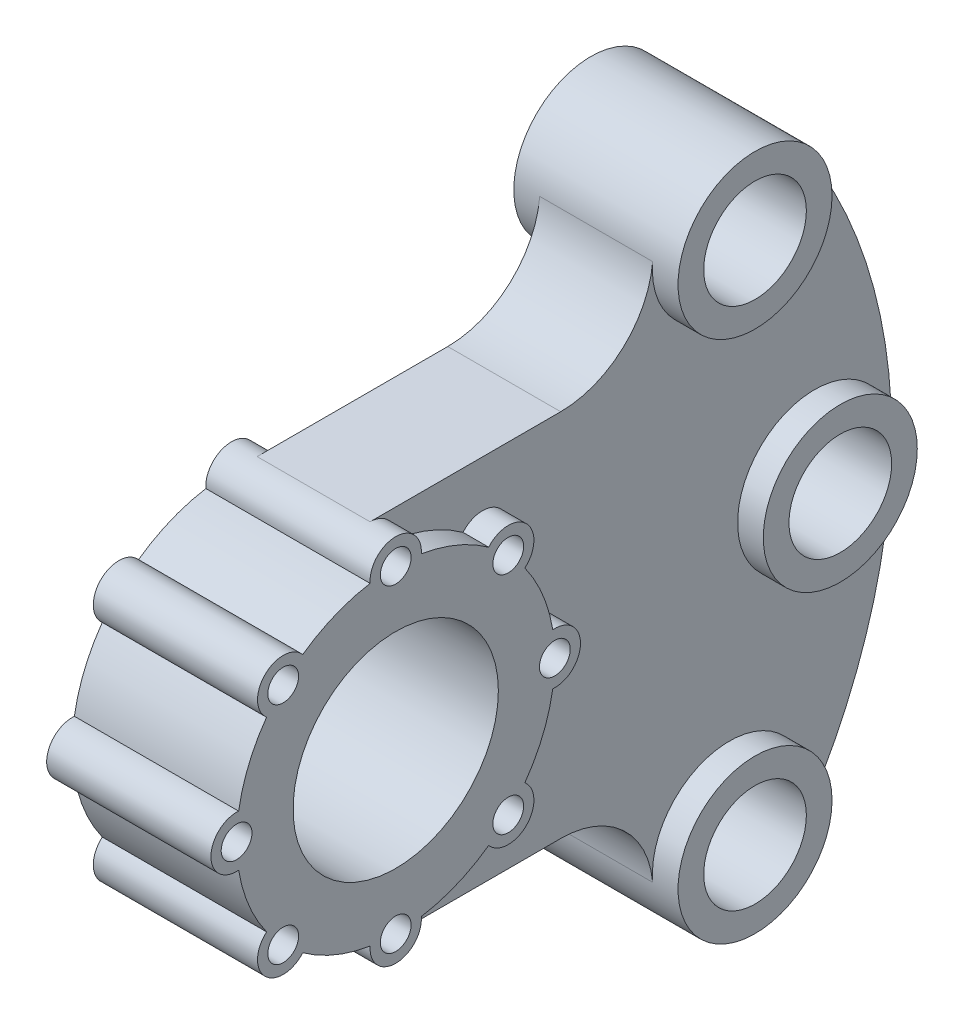
SolidWorks part; units mm, degrees
ref_plane "Front Plane" through (0, 0, 0) normal (1, 0, 0) x (0, 1, 0)
ref_plane "Top Plane" through (0, 0, 0) normal (0, 0, 1) x (0, 1, 0)
ref_plane "Right Plane" through (0, 0, 0) normal (0, 1, 0) x (-1, 0, 0)
sketch "Sketch1" plane through (0, 0, 0) normal (1, 0, 0) x (0, 1, 0)
  line L0 (0, 0) -> (0, -108.5292) construction
  line L2 (51, -70) -> (36, -70) construction
  line L3 (36, 0) -> (36, -5) construction
  line L4 (-36, 0) -> (-36, -37.1366)
  line L5 (36, 0) -> (36, -37.1366)
  circle A0 centre (0, 0) radius 20
  arc A1 (-4.9837, 30.5968) -> (-18.1112, 25.1592) centre (0, 0) ccw
  arc A2 (4.9837, 30.5968) -> (-4.9837, 30.5968) centre (0, 31) ccw
  circle A3 centre (0, 31) radius 3
  arc A4 (25.1592, 18.1112) -> (18.1112, 25.1592) centre (21.9203, 21.9203) ccw
  circle A5 centre (21.9203, 21.9203) radius 3
  arc A6 (30.5968, -4.9837) -> (30.5968, 4.9837) centre (31, 0) ccw
  circle A7 centre (31, 0) radius 3
  arc A8 (18.1112, -25.1592) -> (25.1592, -18.1112) centre (21.9203, -21.9203) ccw
  circle A9 centre (21.9203, -21.9203) radius 3
  arc A10 (-4.9837, -30.5968) -> (4.9837, -30.5968) centre (0, -31) ccw
  circle A11 centre (0, -31) radius 3
  arc A12 (-25.1592, -18.1112) -> (-18.1112, -25.1592) centre (-21.9203, -21.9203) ccw
  circle A13 centre (-21.9203, -21.9203) radius 3
  arc A14 (-30.5968, 4.9837) -> (-30.5968, -4.9837) centre (-31, 0) ccw
  circle A15 centre (-31, 0) radius 3
  arc A16 (-18.1112, 25.1592) -> (-25.1592, 18.1112) centre (-21.9203, 21.9203) ccw
  circle A17 centre (-21.9203, 21.9203) radius 3
  arc A18 (18.1112, 25.1592) -> (4.9837, 30.5968) centre (0, 0) ccw
  arc A19 (18.1112, 25.1592) -> (4.9837, 30.5968) centre (0, 0) ccw
  circle A20 centre (0, -86.6083) radius 10
  arc A21 (30.5968, 4.9837) -> (25.1592, 18.1112) centre (0, 0) ccw
  arc A23 (25.1592, -18.1112) -> (30.5968, -4.9837) centre (0, 0) ccw
  arc A24 (-59.8329, -82.1235) -> (59.8329, -82.1235) centre (0, 0) ccw
  arc A25 (4.9837, -30.5968) -> (18.1112, -25.1592) centre (0, 0) ccw
  arc A26 (59.8329, -82.1235) -> (52.3636, -55.0621) centre (51, -70) ccw
  arc A27 (-18.1112, -25.1592) -> (-4.9837, -30.5968) centre (0, 0) ccw
  circle A28 centre (51, -70) radius 10
  circle A29 centre (-51, -70) radius 10
  arc A30 (-30.5968, -4.9837) -> (-25.1592, -18.1112) centre (0, 0) ccw
  arc A31 (-25.1592, 18.1112) -> (-30.5968, 4.9837) centre (0, 0) ccw
  arc A32 (-59.8329, -82.1235) -> (-52.3636, -55.0621) centre (-51, -70) cw
  arc A33 (-52.3636, -55.0621) -> (-36, -37.1366) centre (-54, -37.1366) ccw
  arc A34 (52.3636, -55.0621) -> (36, -37.1366) centre (54, -37.1366) cw
  point P41 (0, -101.6083)
  point P57 (0, 0)
  point P58 (0, 0)
  dimension "D1" = 62
  dimension "D2" = 40
  dimension "D3" = 10
  dimension "D4" = 6
  dimension "D7" = 20
  dimension "D9" = 36
  dimension "D10" = 20
  dimension "D8" = 70
  dimension "D5" = 8
extrude "Boss-Extrude2" add sketch "Sketch1" along normal mid plane 32 contours A16 A31 A14 A30 A12 A27 A10 A25 A8 A23 A6 A21 A4 A18 A2 A1 A17 A15 A13 A11 A9 A7 A5 A3 A0 region at (0, -33.6996, 2.9269)
extrude "Boss-Extrude13" add sketch "Sketch1<9>" along normal mid plane 22 contours A26 A34 L5 A6 A23 A8 A25 A10 A27 A12 A30 A14 L4 A33 A32 A24 A29 A28 A20 region at (0, 0, -61.5539)
sketch "Sketch1<9>" plane through (0, 0, 0) normal (1, 0, 0) x (0, 1, 0) same geometry as "Sketch1"
sketch "Sketch4" plane through (0, 0, 0) normal (1, 0, 0) x (0, 1, 0)
  circle A0 centre (51, -70) radius 15
  circle A1 centre (51, -70) radius 10
sketch "Sketch5" plane through (0, 0, 0) normal (1, 0, 0) x (0, 1, 0)
  circle A0 centre (0, -86.6083) radius 10
  circle A1 centre (0, -86.6083) radius 15
  circle A2 centre (-51, -70) radius 10
  circle A3 centre (-51, -70) radius 15
  circle A5 centre (51, -70) radius 15
  circle A6 centre (51, -70) radius 10
  dimension "D1" = 30
  dimension "D2" = 20
  dimension "D3" = 30
  dimension "D4" = 20
extrude "Boss-Extrude14" add sketch "Sketch5" along normal mid plane 32
